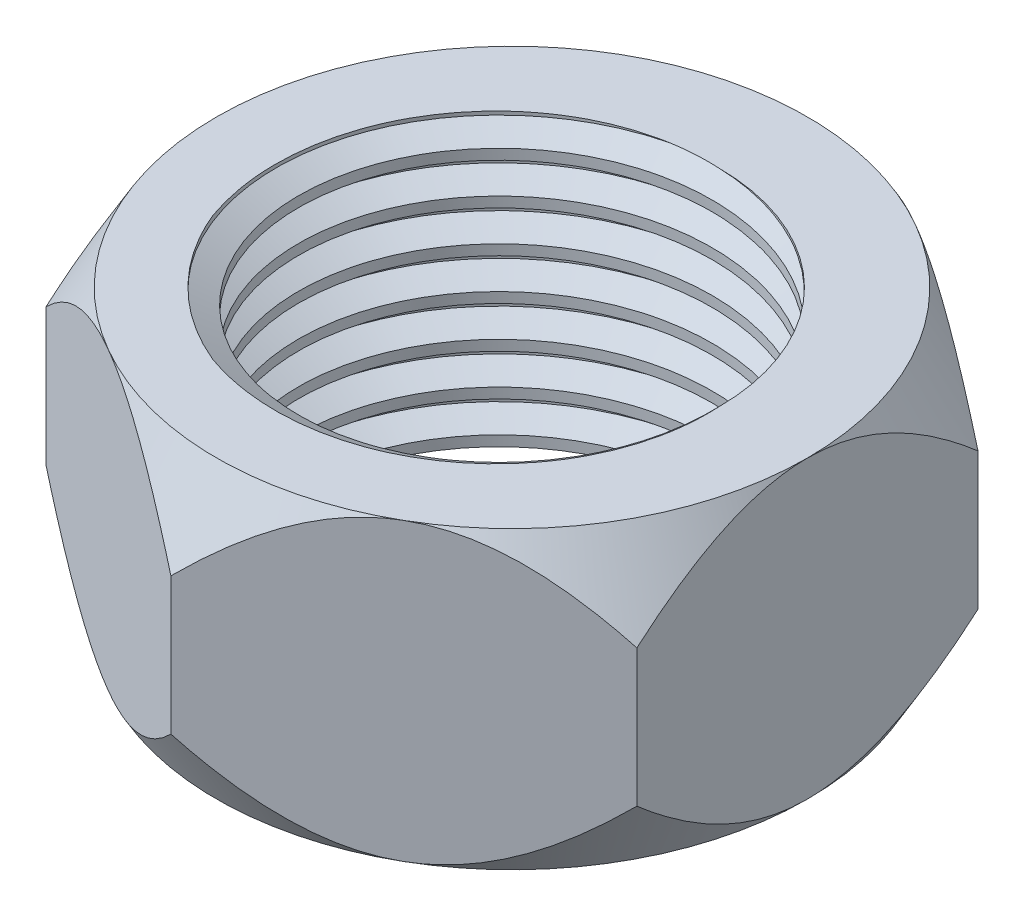
SolidWorks part; units mm, degrees
ref_plane "Front Plane" through (0, 0, 0) normal (0, 0, 1) x (1, 0, 0)
ref_plane "Top Plane" through (0, 0, 0) normal (0, 1, 0) x (1, 0, 0)
ref_plane "Right Plane" through (0, 0, 0) normal (1, 0, 0) x (0, 0, -1)
sketch "Sketch1" plane through (0, 0, 0) normal (0, 1, 0) x (1, 0, 0)
  line L1 (0, 28.8675) -> (-25, 14.4338)
  line L2 (-25, 14.4338) -> (-25, -14.4338)
  line L3 (-25, -14.4338) -> (0, -28.8675)
  line L4 (0, -28.8675) -> (25, -14.4338)
  line L5 (25, -14.4338) -> (25, 14.4338)
  line L6 (25, 14.4338) -> (0, 28.8675)
  circle A0 centre (0, 0) radius 25 construction
  dimension "D1" = 25
extrude "Boss-Extrude1" add sketch "Sketch1" along normal blind 25
sketch "Sketch2" plane through (0, 25, 0) normal (0, 1, 0) x (1, 0, 0)
  circle A0 centre (0, 0) radius 25
extrude "Cut-Extrude1" cut sketch "Sketch2" against normal through all draft 30 flip side to cut
sketch "Sketch3" plane through (0, 0, 0) normal (0, -1, 0) x (1, 0, 0)
  circle A0 centre (0, 0) radius 25
extrude "Cut-Extrude2" cut sketch "Sketch3" against normal through all draft 30 flip side to cut
sketch "Sketch4" plane through (0, 0, 0) normal (0, -1, 0) x (1, 0, 0)
  circle A0 centre (0, 0) radius 17.5
  dimension "D1" = 35
extrude "Cut-Extrude3" cut sketch "Sketch4" against normal through all
thread "Thread1" pitch 3.5 method cut profile "Thread Profile1" start angle 0, offset 3, length 0, pitch 3.5, diameter 35
ref_plane "Plane1" through (17.5, -3, 0) normal (0, 0, 1) x (1, 0, 0)
sketch "Thread Profile1" plane through (17.5, -3, 0) normal (0, 0, 1) x (1, 0, 0)
  line L0 (0, 0) -> (0, 3.5) construction
  line L1 (0, 0) -> (1.8944, 1.0937)
  line L2 (1.8944, 1.0937) -> (1.8944, 1.5312)
  line L3 (1.8944, 1.5312) -> (0, 2.625)
  line L4 (1.8944, 1.3125) -> (0, 1.3125) construction
  line L11 (0, 0) -> (0, 2.625)
  point P2 (0, 0)
  dimension "Pitch" = 3.5
  dimension "Profile_Angle" = 60
  dimension "Profile_Land" = 0.4375
  dimension "Profile_Height" = 1.8944
